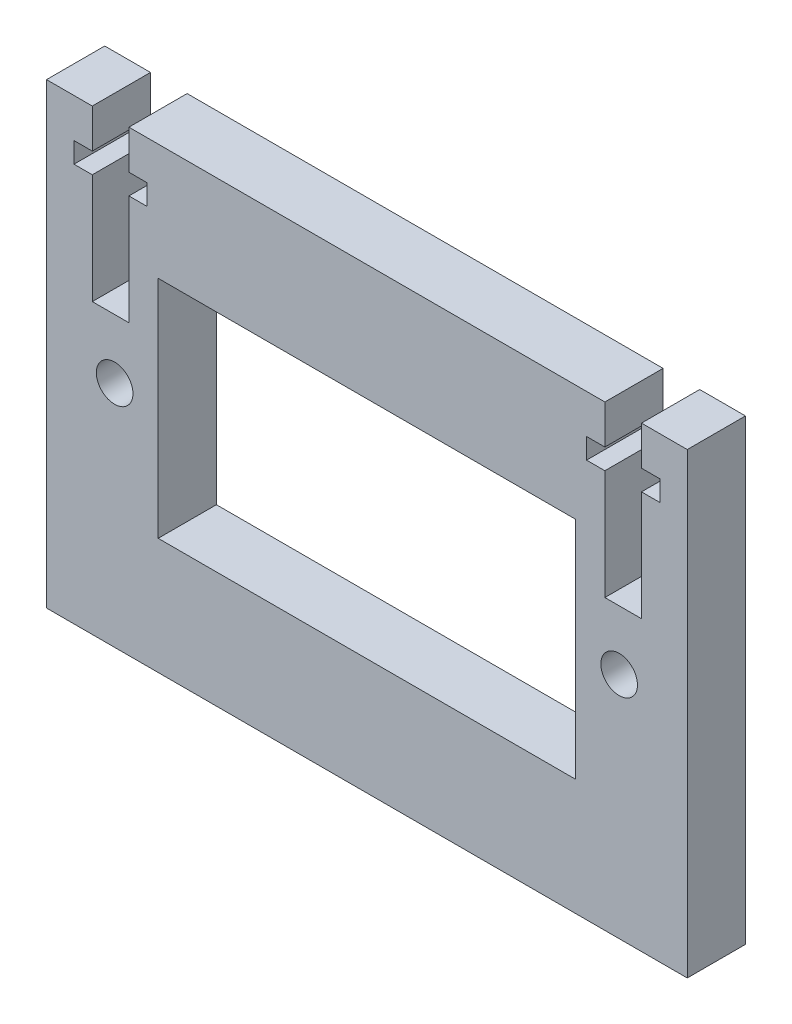
SolidWorks part; units mm, degrees
ref_plane "Front Plane" through (0, 0, 0) normal (0, 0, 1) x (1, 0, 0)
ref_plane "Top Plane" through (0, 0, 0) normal (0, 1, 0) x (1, 0, 0)
ref_plane "Right Plane" through (0, 0, 0) normal (1, 0, 0) x (0, 0, -1)
sketch "Sketch1" plane through (0, 0, 0) normal (0, 0, 1) x (1, 0, 0)
  line L1 (17.5, 12.5) -> (-17.5, 12.5)
  line L2 (17.5, 12.5) -> (17.5, -12.5)
  line L3 (17.5, -12.5) -> (-17.5, -12.5)
  line L4 (-17.5, 12.5) -> (-17.5, -12.5)
  line L5 (17.5, 12.5) -> (-17.5, -12.5) construction
  line L6 (17.5, -12.5) -> (-17.5, 12.5) construction
  point P0 (0, 0)
  dimension "D1" = 35
  dimension "D2" = 25
extrude "Boss-Extrude1" add sketch "Sketch1" along normal blind 3.18
sketch "Sketch2" plane through (0, 0, 3.18) normal (0, 0, 1) x (1, 0, 0)
  line L1 (11.4, 6.15) -> (-11.4, 6.15)
  line L2 (11.4, 6.15) -> (11.4, -6.15)
  line L3 (11.4, -6.15) -> (-11.4, -6.15)
  line L4 (-11.4, 6.15) -> (-11.4, -6.15)
  line L5 (11.4, 6.15) -> (-11.4, -6.15) construction
  line L6 (11.4, -6.15) -> (-11.4, 6.15) construction
  point P0 (0, 0)
  dimension "D1" = 22.8
  dimension "D2" = 12.3
extrude "Cut-Extrude1" cut sketch "Sketch2" against normal blind 3.18
sketch "Sketch3" plane through (0, 0, 3.18) normal (0, 0, 1) x (1, 0, 0)
  line L0 (-11.4, 6.15) -> (-11.4, -6.15) construction
  circle A0 centre (-13.78, 0) radius 1
  dimension "D1" = 2
  dimension "D2" = 2.38
extrude "Cut-Extrude2" cut sketch "Sketch3" against normal blind 3.18
mirror "Mirror1" about plane through (0, 0, 0) normal (1, 0, 0) of "Cut-Extrude2"
sketch "Sketch5" plane through (0, 0, 3.18) normal (0, 0, 1) x (1, 0, 0)
  line L0 (17.5, 12.5) -> (-17.5, 12.5) construction
  line L1 (-13, 12.5) -> (-15, 12.5)
  line L2 (-13, 12.5) -> (-13, 10.368)
  line L3 (-13, 3.248) -> (-15, 3.248)
  line L4 (-15, 12.5) -> (-15, 10.368)
  line L5 (-13, 12.5) -> (-15, 3.248) construction
  line L6 (-13, 3.248) -> (-15, 12.5) construction
  line L7 (-16, 10.368) -> (-15, 10.368)
  line L8 (-16, 10.368) -> (-16, 9.248)
  line L9 (-16, 9.248) -> (-15, 9.248)
  line L10 (-12, 10.368) -> (-12, 9.248)
  line L11 (-16, 10.368) -> (-12, 9.248) construction
  line L12 (-16, 9.248) -> (-12, 10.368) construction
  line L13 (-14, 12.5) -> (-14, 3.248) construction
  line L14 (-17.5, 12.5) -> (-17.5, -12.5) construction
  line L15 (-13, 10.368) -> (-12, 10.368)
  line L16 (-13, 9.248) -> (-13, 3.248)
  line L17 (-13, 9.248) -> (-12, 9.248)
  line L18 (-15, 9.248) -> (-15, 3.248)
  point P0 (-14, 7.874)
  point P5 (-14, 9.808)
  dimension "D1" = 2
  dimension "D2" = 4
  dimension "D3" = 1.12
  dimension "D4" = 9.252
  dimension "D5" = 6
  dimension "D6" = 2.5
extrude "Cut-Extrude4" cut sketch "Sketch5" against normal blind 3.18
mirror "Mirror2" about plane through (0, 0, 0) normal (1, 0, 0) of "Cut-Extrude4"
